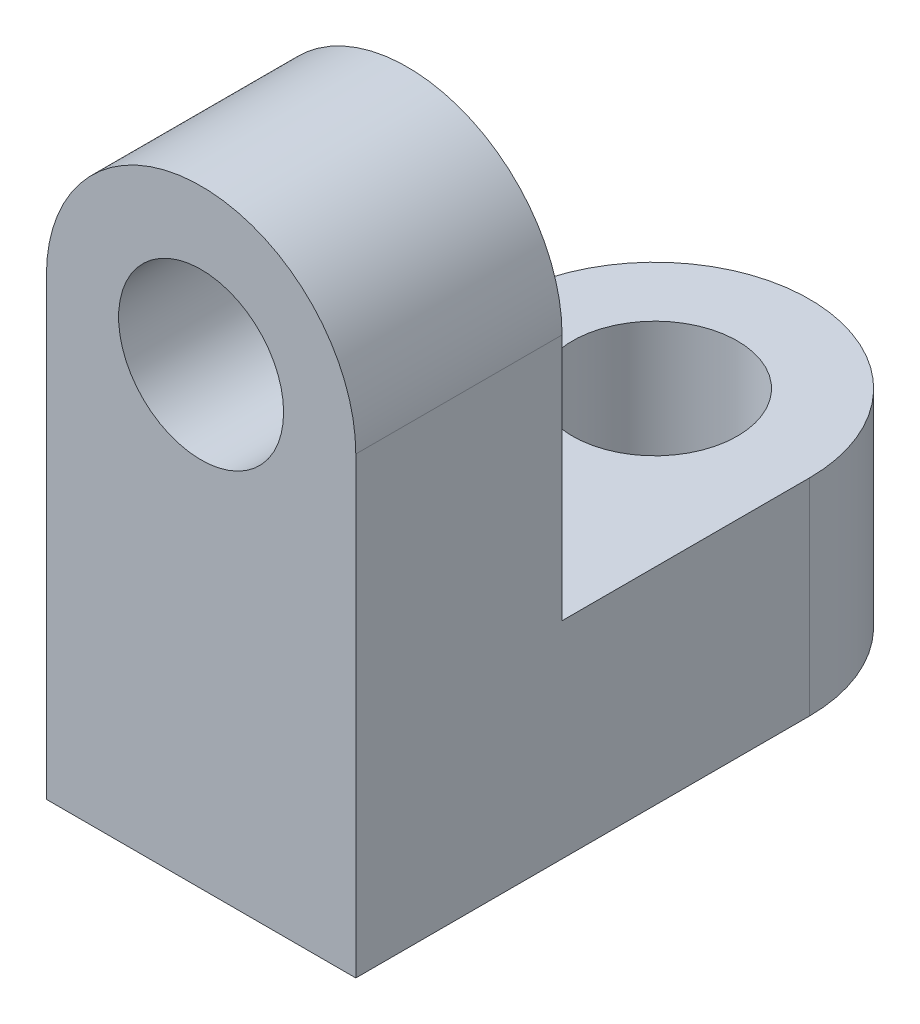
SolidWorks part; units mm, degrees
ref_plane "Front Plane" through (0, 0, 0) normal (0, 0, 1) x (1, 0, 0)
ref_plane "Top Plane" through (0, 0, 0) normal (0, 1, 0) x (1, 0, 0)
ref_plane "Right Plane" through (0, 0, 0) normal (1, 0, 0) x (0, 0, -1)
sketch "Sketch1" plane through (0, 0, 0) normal (0, 0, 1) x (1, 0, 0)
  line L0 (7.5, 0) -> (7.5, -12)
  line L1 (7.5, -12) -> (-7.5, -12)
  line L2 (-7.5, -12) -> (-7.5, 0)
  circle A0 centre (0, 0) radius 4
  arc A1 (7.5, 0) -> (-7.5, 0) centre (0, 0) ccw
  point P4 (7.5, 0)
  point P5 (-14.8619, 0.5484)
  dimension "D1" = 8
  dimension "D3" = 12
  dimension "D2" = 15
extrude "Boss-Extrude1" add sketch "Sketch1" along normal blind 10
sketch "Sketch3" plane through (-7.5, 0, 0) normal (-1, 0, 0) x (0, 0, 1)
  line L0 (0, -12) -> (10, -22)
  line L1 (10, -22) -> (10, -12)
  line L2 (10, -12) -> (0, -12) construction
  line L3 (0, -12) -> (10, -12)
  dimension "D1" = 45
extrude "Boss-Extrude2" add sketch "Sketch3" against normal up to surface (15 mm away) up to face at (7.5, -6, 5)
mirror "Mirror6" about plane through (21.6421, -12, 0) normal (0, -0.7071, -0.7071) of bodies 103
